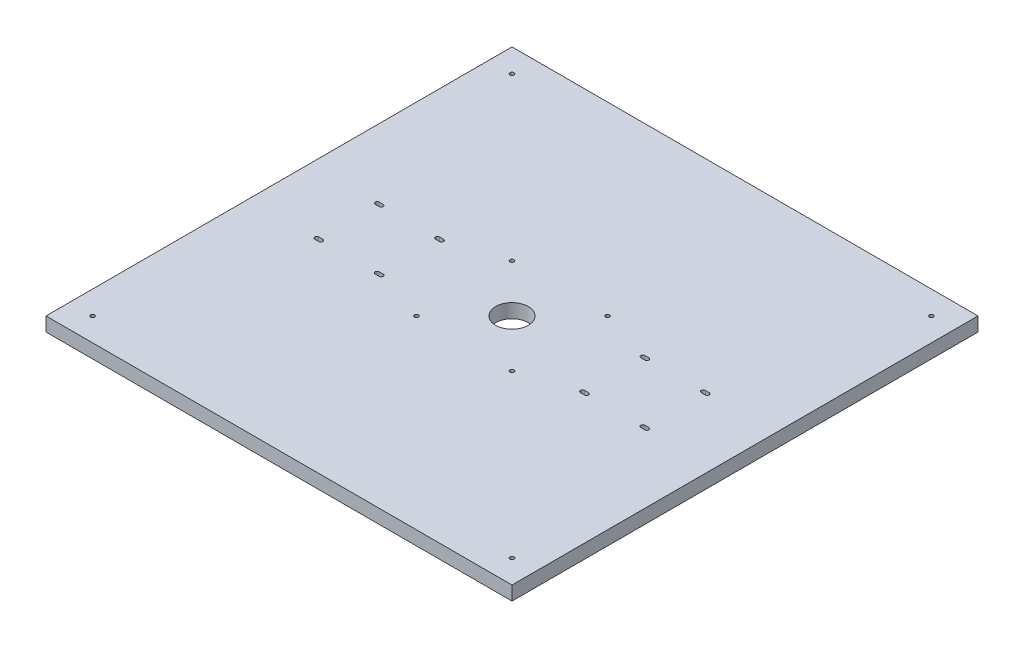
SolidWorks part; units mm, degrees
material "5052-H32"
ref_plane "Alzado" through (0, 0, 0) normal (0, 0, 1) x (1, 0, 0)
ref_plane "Planta" through (0, 0, 0) normal (0, 1, 0) x (1, 0, 0)
ref_plane "Vista lateral" through (0, 0, 0) normal (1, 0, 0) x (0, 0, -1)
sketch "Croquis1" plane through (0, 0, 0) normal (0, 1, 0) x (1, 0, 0)
  line L1 (-250, -250) -> (250, -250)
  line L2 (-250, -250) -> (-250, 250)
  line L3 (-250, 250) -> (250, 250)
  line L4 (250, -250) -> (250, 250)
  point P6 (0, -250)
  point P8 (-250, 0)
  dimension "D1" = 500
  dimension "D2" = 500
extrude "Saliente-Extruir1" add sketch "Croquis1" along normal blind 15
sketch "Croquis2" plane through (0, 15, 0) normal (0, 1, 0) x (1, 0, 0)
  line L0 (0, 250) -> (0, -250) construction
  line L1 (250, 250) -> (-250, 250) construction
  line L2 (-250, -250) -> (250, -250) construction
  line L3 (-250, 0) -> (250, 0) construction
  line L4 (-250, 250) -> (-250, -250) construction
  line L5 (250, -250) -> (250, 250) construction
  circle A0 centre (-225, 225) radius 2.15
  circle A1 centre (225, 225) radius 2.15
  circle A2 centre (225, -225) radius 2.15
  circle A3 centre (-225, -225) radius 2.15
  dimension "D3" = 4.3
  dimension "D1" = 25
  dimension "D2" = 25
extrude "Cortar-Extruir1" cut sketch "Croquis2" against normal up to surface (15 mm away) up to face at (0, 0, 0)
sketch "Croquis3" plane through (0, 15, 0) normal (0, 1, 0) x (1, 0, 0)
  line L0 (0, 250) -> (0, -250) construction
  line L1 (-250, 0) -> (250, 0) construction
  line L2 (-250, 250) -> (-250, -250) construction
  line L3 (250, -250) -> (250, 250) construction
  line L4 (-177.115, -32.4) -> (-172.815, -32.4) construction
  line L5 (250, 250) -> (-250, 250) construction
  line L6 (-250, -250) -> (250, -250) construction
  line L7 (-177.115, 32.4) -> (-172.815, 32.4) construction
  line L8 (-51.265, 51.265) -> (51.265, 51.265) construction
  line L9 (-51.265, 51.265) -> (-51.265, -51.265) construction
  line L10 (-51.265, -51.265) -> (51.265, -51.265) construction
  line L11 (51.265, 51.265) -> (51.265, -51.265) construction
  line L12 (-177.115, 34.55) -> (-172.815, 34.55)
  line L13 (-174.965, -32.4) -> (-110.165, -32.4) construction
  line L14 (-174.965, -32.4) -> (-174.965, 32.4) construction
  line L15 (-174.965, 32.4) -> (-110.165, 32.4) construction
  line L16 (-110.165, -32.4) -> (-110.165, 32.4) construction
  line L17 (-177.115, -30.25) -> (-172.815, -30.25)
  line L18 (-177.115, -34.55) -> (-172.815, -34.55)
  line L19 (-112.315, -32.4) -> (-108.015, -32.4) construction
  line L20 (-177.115, 30.25) -> (-172.815, 30.25)
  line L21 (-112.315, -30.25) -> (-108.015, -30.25)
  line L22 (-112.315, -34.55) -> (-108.015, -34.55)
  line L23 (-112.315, 32.4) -> (-108.015, 32.4) construction
  line L24 (-112.315, 34.55) -> (-108.015, 34.55)
  line L25 (-112.315, 30.25) -> (-108.015, 30.25)
  line L26 (177.115, -32.4) -> (172.815, -32.4) construction
  line L27 (177.115, -30.25) -> (172.815, -30.25)
  line L28 (177.115, -34.55) -> (172.815, -34.55)
  line L29 (177.115, 32.4) -> (172.815, 32.4) construction
  line L30 (177.115, 34.55) -> (172.815, 34.55)
  line L31 (177.115, 30.25) -> (172.815, 30.25)
  line L32 (112.315, -32.4) -> (108.015, -32.4) construction
  line L33 (112.315, -30.25) -> (108.015, -30.25)
  line L34 (112.315, -34.55) -> (108.015, -34.55)
  line L35 (112.315, 32.4) -> (108.015, 32.4) construction
  line L36 (112.315, 34.55) -> (108.015, 34.55)
  line L37 (112.315, 30.25) -> (108.015, 30.25)
  arc A0 (-177.115, 34.55) -> (-177.115, 30.25) centre (-177.115, 32.4) ccw
  arc A1 (-172.815, 30.25) -> (-172.815, 34.55) centre (-172.815, 32.4) ccw
  circle A2 centre (-51.265, 51.265) radius 2.15
  circle A3 centre (-51.265, -51.265) radius 2.15
  circle A4 centre (51.265, -51.265) radius 2.15
  circle A5 centre (51.265, 51.265) radius 2.15
  arc A6 (-177.115, -30.25) -> (-177.115, -34.55) centre (-177.115, -32.4) ccw
  arc A7 (-172.815, -34.55) -> (-172.815, -30.25) centre (-172.815, -32.4) ccw
  arc A8 (-112.315, -30.25) -> (-112.315, -34.55) centre (-112.315, -32.4) ccw
  arc A9 (-108.015, -34.55) -> (-108.015, -30.25) centre (-108.015, -32.4) ccw
  arc A10 (-112.315, 34.55) -> (-112.315, 30.25) centre (-112.315, 32.4) ccw
  arc A11 (-108.015, 30.25) -> (-108.015, 34.55) centre (-108.015, 32.4) ccw
  arc A12 (177.115, -30.25) -> (177.115, -34.55) centre (177.115, -32.4) cw
  arc A13 (172.815, -34.55) -> (172.815, -30.25) centre (172.815, -32.4) cw
  arc A14 (177.115, 34.55) -> (177.115, 30.25) centre (177.115, 32.4) cw
  arc A15 (172.815, 30.25) -> (172.815, 34.55) centre (172.815, 32.4) cw
  arc A16 (112.315, -30.25) -> (112.315, -34.55) centre (112.315, -32.4) cw
  arc A17 (108.015, -34.55) -> (108.015, -30.25) centre (108.015, -32.4) cw
  arc A18 (112.315, 34.55) -> (112.315, 30.25) centre (112.315, 32.4) cw
  arc A19 (108.015, 30.25) -> (108.015, 34.55) centre (108.015, 32.4) cw
  point P10 (-174.965, 32.4)
  point P17 (0, -51.265)
  point P22 (-51.265, 0)
  point P23 (-174.965, 0)
  point P28 (-110.165, 0)
  point P31 (-174.965, -32.4)
  point P43 (-110.165, -32.4)
  point P50 (-110.165, 32.4)
  point P62 (174.965, -32.4)
  point P69 (174.965, 32.4)
  point P76 (110.165, -32.4)
  point P83 (110.165, 32.4)
  point P88 (110.165, 0)
  dimension "D3" = 4.3
  dimension "D7" = 4.3
  dimension "D8" = 64.8
  dimension "D12" = 4.3
  dimension "D2" = 4.3
  dimension "D4" = 102.53
  dimension "D5" = 102.53
  dimension "D6" = 4.3
  dimension "D9" = 64.8
  dimension "D10" = 58.9
  dimension "D11" = 4.3
  dimension "D13" = 4.3
  dimension "D14" = 4.3
  dimension "D15" = 4.3
extrude "Cortar-Extruir3" cut sketch "Croquis3" against normal up to surface (15 mm away) up to face at (-225, 0, 222.85)
sketch "Croquis4" plane through (0, 15, 0) normal (0, 1, 0) x (1, 0, 0)
  line L0 (-51.265, -51.265) -> (51.265, 51.265) construction
  circle A0 centre (0, 0) radius 17.5
  dimension "D1" = 35
extrude "Cortar-Extruir4" cut sketch "Croquis4" against normal blind 40
sketch "Sketch2" [suppressed] plane through (0, 15, 0) normal (0, 1, 0) x (1, 0, 0)
  circle A0 centre (26.25, 494.75) radius 2.1
  circle A1 centre (26.25, 359.25) radius 2.1
  circle A2 centre (316.75, 494.75) radius 2.1
  circle A3 centre (316.75, 359.25) radius 2.1
  circle A4 centre (176.75, 494.75) radius 2.1
  circle A5 centre (166.25, 494.75) radius 2.1
  circle A6 centre (166.25, 359.25) radius 2.1
  circle A7 centre (176.75, 359.25) radius 2.1
extrude "Cut-Extrude1" [suppressed] cut sketch "Sketch2" against normal up to next
